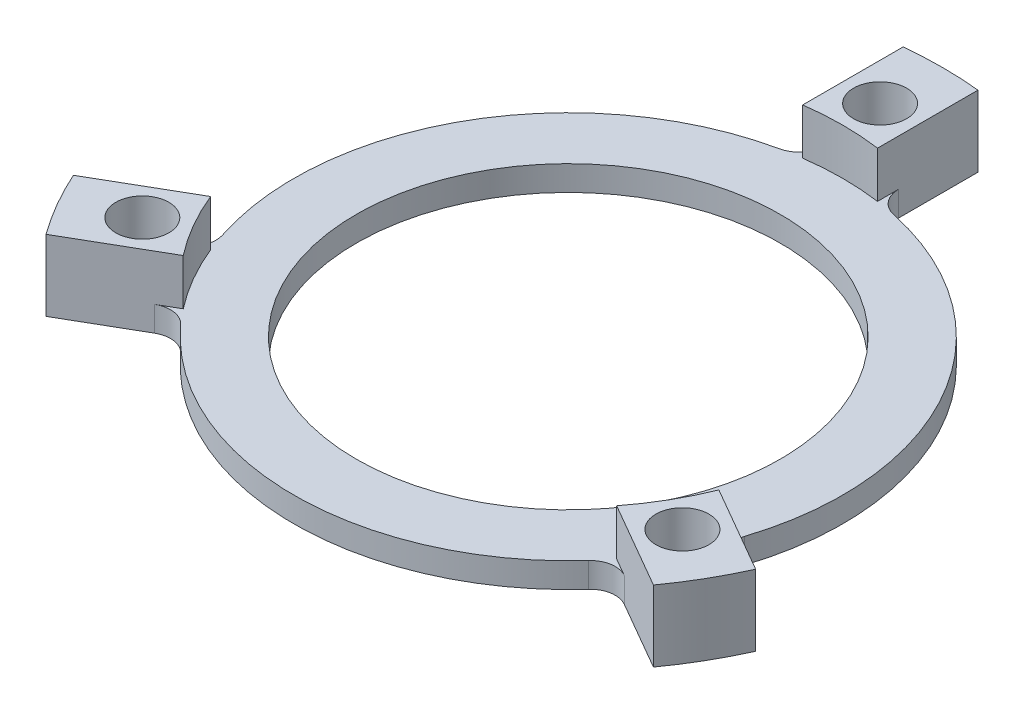
SolidWorks part; units mm, degrees
material "Delrin 2700 NC010, Low Viscosity Acetal Copolymer (SS)"
ref_plane "Front" through (0, 0, 0) normal (0, 0, 1) x (1, 0, 0)
ref_plane "Top" through (0, 0, 0) normal (0, 1, 0) x (1, 0, 0)
ref_plane "Right" through (0, 0, 0) normal (1, 0, 0) x (0, 0, -1)
sketch "Sketch1" plane through (0, 0, 0) normal (0, 1, 0) x (1, 0, 0)
  line L0 (0, 11) -> (0, 15) construction
  line L1 (-1.5, 15) -> (1.5, 15)
  line L2 (-1.5, 15) -> (-1.5, 10.8972)
  line L3 (1.5, 15) -> (1.5, 10.8972)
  line L4 (12.2404, -8.799) -> (8.6873, -6.7477)
  line L5 (13.7404, -6.201) -> (10.1873, -4.1496)
  line L6 (13.7404, -6.201) -> (12.2404, -8.799)
  line L7 (-13.7404, -6.201) -> (-10.1873, -4.1496)
  line L8 (-12.2404, -8.799) -> (-8.6873, -6.7477)
  line L9 (-12.2404, -8.799) -> (-13.7404, -6.201)
  circle A0 centre (0, 0) radius 11
  circle A1 centre (0, 0) radius 15
  circle A2 centre (0, 12.5) radius 1.0635
  circle A5 centre (0, 0) radius 8.5
  circle A6 centre (10.8253, -6.25) radius 1.0635
  circle A7 centre (-10.8253, -6.25) radius 1.0635
  point P12 (0, 15)
  dimension "D1" = 22
  dimension "D2" = 2.127
  dimension "D3" = 30
  dimension "D5" = 17
  dimension "D4" = 3
  dimension "D7" = 12.5
  dimension "D6" = 3
extrude "Boss-Extrude1" add sketch "Sketch1" along normal blind 2.85 contours L7 A1 L8 A0 A7 | A0 L0 A2 A1 L2 | L0 A0 L3 A1 A2 | L4 A1 L5 A0 A6 region at (-0.8764, 0, -13.1675) region at (0.8764, 0, -13.1675) region at (-9.5851, 0, 5.534) region at (11.8973, 0, 5.2153)
extrude "Boss-Extrude2" add sketch "Sketch1<3>" along normal blind 1 contours A0 A5 region at (0, 0, -10.6889)
sketch "Sketch1<3>" plane through (0, 0, 0) normal (0, 1, 0) x (1, 0, 0) same geometry as "Sketch1"
fillet "Fillet1" radius 1 6 edges at (1.5, 0.5, -10.8972) (10.1873, 0.5, 4.1496) (8.6873, 0.5, 6.7477) (-1.5, 0.5, -10.8972) (-10.1873, 0.5, 4.1496) (-8.6873, 0.5, 6.7477)
